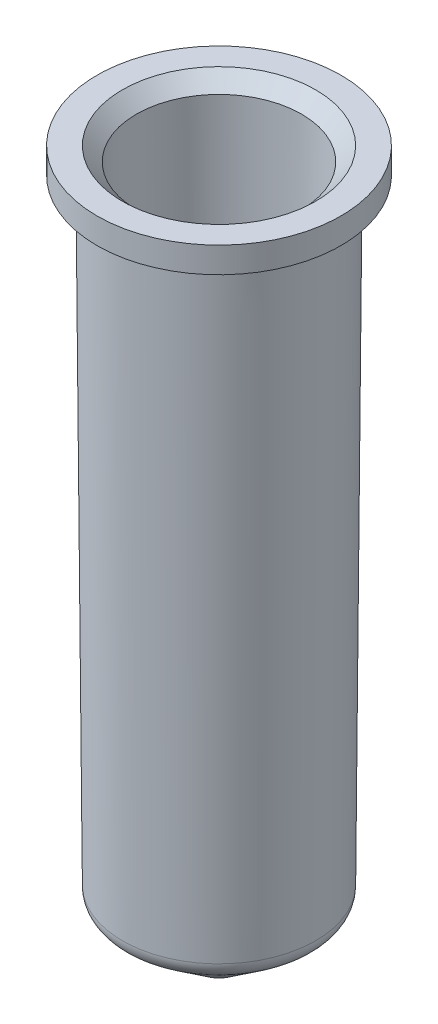
SolidWorks part; units mm, degrees
ref_plane "Front Plane" through (0, 0, 0) normal (0, 0, 1) x (1, 0, 0)
ref_plane "Top Plane" through (0, 0, 0) normal (0, 1, 0) x (1, 0, 0)
ref_plane "Right Plane" through (0, 0, 0) normal (1, 0, 0) x (0, 0, -1)
sketch "Sketch1" plane through (0, 0, 0) normal (0, 0, 1) x (1, 0, 0)
  line L0 (0, 0) -> (0, 36.0603) construction
  line L1 (1.1973, -3.458) -> (4.7524, -0.801)
  line L2 (5.1537, -0.0075) -> (5.4, 32.774)
  line L3 (4.1538, 0) -> (4.4046, 33.394)
  line L4 (0.5986, -2.657) -> (4.1538, 0)
  line L5 (5.1546, 34.144) -> (6.5046, 34.144)
  line L6 (6.5046, 34.144) -> (6.5046, 32.774)
  line L7 (6.5046, 32.774) -> (5.4, 32.774)
  line L8 (5.1537, -0.0075) -> (5.4179, 35.1598) construction
  line L9 (4.1538, 0) -> (4.418, 35.1674) construction
  line L10 (4.4046, 33.394) -> (5.1546, 34.144)
  line L11 (0, -3.856) -> (0, -2.856)
  arc A0 (1.1973, -3.458) -> (0, -3.856) centre (0, -1.856) cw
  arc A1 (4.7524, -0.801) -> (5.1537, -0.0075) centre (4.1538, 0) ccw
  arc A2 (4.1538, 0) -> (4.1538, 0) centre (4.1538, 0) ccw
  arc A3 (0.5986, -2.657) -> (0, -2.856) centre (0, -1.856) cw
  point P6 (0, 0)
  point P9 (0, -2.3188)
  point P10 (0.6309, -3.7539)
  point P13 (5.15, -0.5039)
  point P26 (0, 0)
  point P27 (0, 0)
  dimension "D3" = 2
  dimension "D5" = 1
  dimension "D1" = 5.15
  dimension "D2" = 1.37
  dimension "D4" = 3.25
  dimension "D7" = 5.4
  dimension "D8" = 38
  dimension "D9" = 2.1
  dimension "D10" = 135
  dimension "D11" = 0.75
  dimension "D6" = 1
revolve "Revolve1" add sketch "Sketch1" angle 360 about L0
